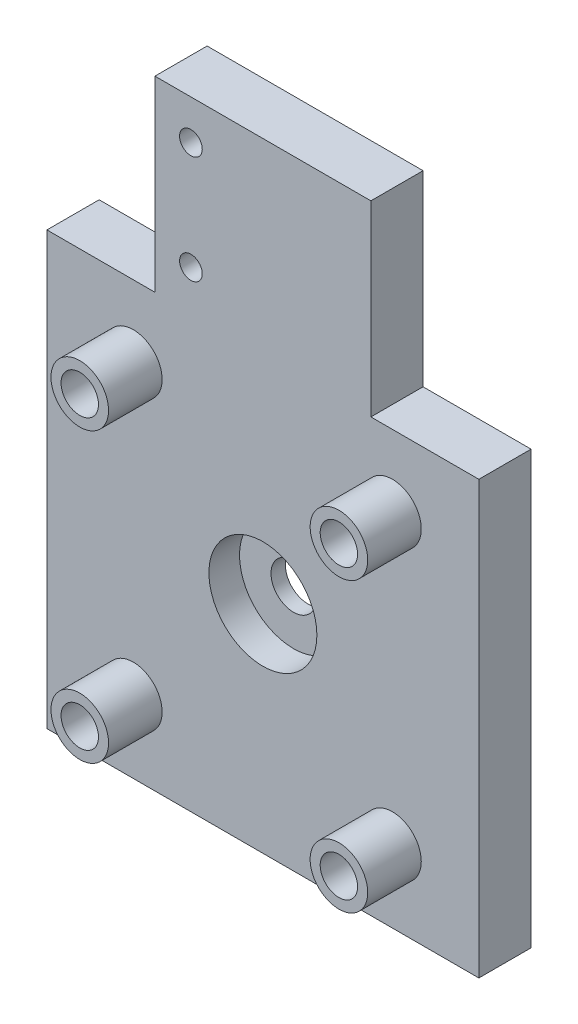
SolidWorks part; units mm, degrees
ref_plane "Front Plane" through (0, 0, 0) normal (0, 0, 1) x (1, 0, 0)
ref_plane "Top Plane" through (0, 0, 0) normal (0, 1, 0) x (1, 0, 0)
ref_plane "Right Plane" through (0, 0, 0) normal (1, 0, 0) x (0, 0, -1)
sketch "Sketch1" plane through (0, 0, 0) normal (0, 0, 1) x (1, 0, 0)
  line L1 (-19.05, -38.1) -> (19.05, -38.1)
  line L2 (-19.05, -38.1) -> (-19.05, 38.1)
  line L3 (-19.05, 38.1) -> (19.05, 38.1)
  line L4 (19.05, -38.1) -> (19.05, 38.1)
  line L5 (-19.05, -38.1) -> (19.05, 38.1) construction
  line L6 (-19.05, 38.1) -> (19.05, -38.1) construction
  point P0 (0, 0)
  dimension "D1" = 38.1
  dimension "D2" = 76.2
extrude "Boss-Extrude1" add sketch "Sketch1" along normal blind 7.9375
sketch "Sketch2" plane through (0, 0, 7.9375) normal (0, 0, 1) x (1, 0, 0)
  circle A0 centre (0, 0) radius 3.9688
  dimension "D1" = 7.9375
extrude "Cut-Extrude1" cut sketch "Sketch2" against normal through all
sketch "Sketch4" plane through (0, 0, 7.9375) normal (0, 0, 1) x (1, 0, 0)
  circle A0 centre (0, 0) radius 9.525
  dimension "D1" = 19.05
extrude "Cut-Extrude2" cut sketch "Sketch4" against normal offset from surface (5.3975 mm away) 2.54 up to face at (3.9688, 0, 0)
sketch "Sketch8" plane through (0, 0, 7.9375) normal (0, 0, 1) x (1, 0, 0)
  line L0 (19.05, 38.1) -> (-19.05, 38.1) construction
  line L1 (-19.05, 38.1) -> (-38.1, 38.1)
  line L2 (-19.05, 38.1) -> (-19.05, -38.1)
  line L3 (-19.05, -38.1) -> (-38.1, -38.1)
  line L4 (-38.1, 38.1) -> (-38.1, -38.1)
  line L5 (-19.05, 38.1) -> (-19.05, -38.1) construction
  line L6 (-19.05, -38.1) -> (19.05, -38.1) construction
  line L7 (0, 38.1) -> (0, -38.1) construction
  line L8 (19.05, -38.1) -> (38.1, -38.1)
  line L9 (38.1, 38.1) -> (38.1, -38.1)
  line L10 (19.05, 38.1) -> (38.1, 38.1)
  line L11 (19.05, 38.1) -> (19.05, -38.1)
  dimension "D1" = 38.1
extrude "Boss-Extrude5" add sketch "Sketch8" against normal up to surface (7.9375 mm away) up to face at (3.9688, 0, 0)
sketch "Sketch5" plane through (0, 0, 7.9375) normal (0, 0, 1) x (1, 0, 0)
  line L0 (38.1, 38.1) -> (-38.1, 38.1) construction
  line L1 (0, 38.1) -> (0, -38.1) construction
  line L2 (38.1, 38.1) -> (-38.1, 38.1) construction
  line L3 (-38.1, -38.1) -> (38.1, -38.1) construction
  circle A0 centre (22.86, 25.4) radius 5.08
  circle A1 centre (-22.86, 25.4) radius 5.08
  point P2 (19.2017, 25.4)
  dimension "D1" = 10.16
  dimension "D2" = 12.7
  dimension "D3" = 22.86
extrude "Boss-Extrude2" add sketch "Sketch5" along normal blind 9.4488
sketch "Sketch6" plane through (0, 0, 17.3863) normal (0, 0, 1) x (1, 0, 0)
  line L0 (0, 38.1) -> (0, -38.1) construction
  line L1 (38.1, 38.1) -> (-38.1, 38.1) construction
  line L2 (-38.1, -38.1) -> (38.1, -38.1) construction
  circle A0 centre (22.86, 25.4) radius 3.302
  circle A1 centre (-22.86, 25.4) radius 3.302
  dimension "D1" = 6.604
extrude "Cut-Extrude3" cut sketch "Sketch6" against normal through all
mirror "Mirror1" about plane through (0, 0, 0) normal (0, 1, 0) of "Cut-Extrude3", "Boss-Extrude2"
sketch "Sketch7" plane through (0, 0, 7.9375) normal (0, 0, 1) x (1, 0, 0)
  line L0 (0, 71.12) -> (0, -38.1) construction
  line L1 (-19.05, 38.1) -> (19.05, 38.1)
  line L2 (-19.05, 38.1) -> (-19.05, 71.12)
  line L3 (-19.05, 71.12) -> (19.05, 71.12)
  line L4 (19.05, 38.1) -> (19.05, 71.12)
  line L6 (-19.05, 54.61) -> (19.05, 54.61) construction
  line L7 (-12.7, 71.12) -> (-12.7, 38.1) construction
  line L8 (-38.1, -38.1) -> (38.1, -38.1) construction
  line L9 (38.1, 38.1) -> (-38.1, 38.1) construction
  circle A0 centre (-12.7, 64.135) radius 2
  circle A1 centre (-12.7, 45.085) radius 2
  point P17 (0, 74.3341)
  dimension "D3" = 4
  dimension "D1" = 33.02
  dimension "D2" = 6.35
  dimension "D4" = 9.525
  dimension "D5" = 38.1
extrude "Boss-Extrude4" add sketch "Sketch7" against normal up to surface (7.9375 mm away) up to face at (26.162, -25.4, 0)
sketch "Sketch9" plane through (0, 0, 0) normal (0, 0, -1) x (-1, 0, 0)
  line L1 (-12.7, -12.7) -> (12.7, -12.7)
  line L2 (-12.7, -12.7) -> (-12.7, 12.7)
  line L3 (-12.7, 12.7) -> (12.7, 12.7)
  line L4 (12.7, -12.7) -> (12.7, 12.7)
  line L5 (-12.7, -12.7) -> (12.7, 12.7) construction
  line L6 (-12.7, 12.7) -> (12.7, -12.7) construction
  line L22 (-19.05, 38.1) -> (-38.1, 38.1)
  line L23 (-38.1, 38.1) -> (-38.1, -38.1)
  line L24 (-38.1, -38.1) -> (38.1, -38.1)
  line L25 (38.1, -38.1) -> (38.1, 38.1)
  line L26 (38.1, 38.1) -> (19.05, 38.1)
  line L27 (19.05, 38.1) -> (19.05, 71.12)
  line L28 (19.05, 71.12) -> (-19.05, 71.12)
  line L29 (-19.05, 71.12) -> (-19.05, 38.1)
  line L30 (-19.05, 38.1) -> (-38.1, 38.1)
  line L31 (-38.1, 38.1) -> (-38.1, -38.1)
  line L32 (-38.1, -38.1) -> (38.1, -38.1)
  line L33 (38.1, -38.1) -> (38.1, 38.1)
  line L34 (38.1, 38.1) -> (19.05, 38.1)
  line L35 (19.05, 38.1) -> (19.05, 71.12)
  line L36 (19.05, 71.12) -> (-19.05, 71.12)
  line L37 (-19.05, 71.12) -> (-19.05, 38.1)
  circle A0 centre (-22.86, -25.4) radius 3.302 construction
  circle A1 centre (22.86, -25.4) radius 3.302 construction
  circle A2 centre (22.86, 25.4) radius 3.302 construction
  circle A3 centre (12.7, 64.135) radius 2 construction
  circle A4 centre (12.7, 45.085) radius 2 construction
  circle A5 centre (-22.86, 25.4) radius 3.302 construction
  circle A6 centre (-22.86, -25.4) radius 3.302
  circle A7 centre (22.86, -25.4) radius 3.302
  circle A8 centre (22.86, 25.4) radius 3.302
  circle A9 centre (12.7, 64.135) radius 2
  circle A10 centre (12.7, 45.085) radius 2
  circle A11 centre (-22.86, 25.4) radius 3.302
  point P0 (0, 0)
  dimension "D1" = 25.4
  dimension "D2" = 25.4
  dimension "D3" = 0
extrude "Boss-Extrude6" add sketch "Sketch9" along normal blind 1.27 contours L30 L31 L32 L33 L34 L35 L36 L37 | A11 | L2 L1 L4 L3 | A8 | A10 | A9 | A7 | A6
